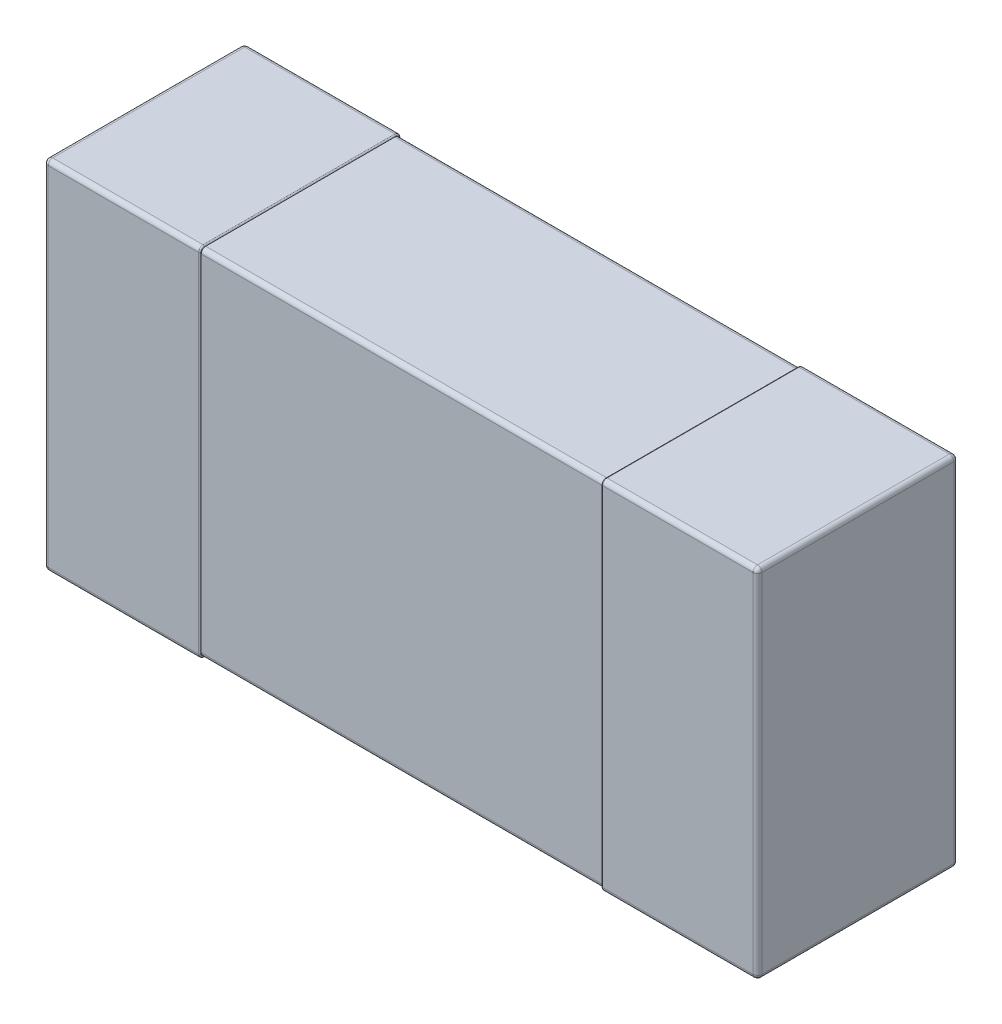
SolidWorks part; units mm, degrees
ref_plane "Top Plane" through (0, 0, 0) normal (0, 0, 1) x (1, 0, 0)
ref_plane "Front Plane" through (0, 0, 0) normal (0, 1, 0) x (1, 0, 0)
ref_plane "Side Plane" through (0, 0, 0) normal (1, 0, 0) x (0, 0, -1)
sketch "Sketch1" plane through (0, 0, 0) normal (0, 0, 1) x (1, 0, 0)
  line L1 (-0.8, 0.4) -> (0.8, 0.4)
  line L2 (-0.8, 0.4) -> (-0.8, -0.4)
  line L3 (-0.8, -0.4) -> (0.8, -0.4)
  line L4 (0.8, 0.4) -> (0.8, -0.4)
  dimension "D1" = 1.6
  dimension "D2" = 0.8
  dimension "D3" = 0.8
  dimension "D4" = 0.4
extrude "All body" add sketch "Sketch1" along normal blind 0.45
sketch "Sketch2" plane through (0, 0, 0) normal (1, 0, 0) x (0, 0, -1)
  line L14 (-0.003, 0.397) -> (-0.447, 0.397)
  line L15 (-0.003, -0.397) -> (-0.003, 0.397)
  line L16 (-0.447, -0.397) -> (-0.003, -0.397)
  line L17 (-0.447, 0.397) -> (-0.447, -0.397)
  line L18 (-0.003, 0.397) -> (-0.447, 0.397)
  line L19 (-0.003, -0.397) -> (-0.003, 0.397)
  line L20 (-0.447, -0.397) -> (-0.003, -0.397)
  line L21 (-0.447, 0.397) -> (-0.447, -0.397)
  dimension "D1" = 0.003
extrude "Cut out the body for pin" cut sketch "Sketch2" against normal blind 0.45 and the other way blind 0.45 flip side to cut
fillet "Body fillet" radius 0.01 4 edges at (0, 0.397, 0.003) (0, 0.397, 0.447) (0, -0.397, 0.003) (0, -0.397, 0.447)
fillet "Pin fillet a" radius 0.01 16 edges at (0.8, -0.4, 0.225) (0.8, 0, 0.45) (0.8, 0.4, 0.225) (0.8, 0, 0) (-0.8, 0.4, 0.225) (-0.8, 0, 0.45) (-0.8, -0.4, 0.225) (-0.8, 0, 0) (0.625, 0.4, 0.45) (0.625, -0.4, 0.45) (0.625, -0.4, 0) (0.625, 0.4, 0) (-0.625, 0.4, 0) (-0.625, -0.4, 0) (-0.625, 0.4, 0.45) (-0.625, -0.4, 0.45)
fillet "Pin fillet b" radius 0.003 16 edges at (0.45, -0.3971, 0.4471) (0.45, -0.4, 0.225) (0.45, -0.3971, 0.0029) (0.45, 0, 0) (0.45, 0.3971, 0.0029) (0.45, 0.4, 0.225) (0.45, 0.3971, 0.4471) (-0.45, -0.3971, 0.4471) (-0.45, -0.4, 0.225) (-0.45, -0.3971, 0.0029) (-0.45, 0, 0) (-0.45, 0.3971, 0.0029) (-0.45, 0.4, 0.225) (-0.45, 0.3971, 0.4471) (0.45, 0, 0.45) (-0.45, 0, 0.45)
